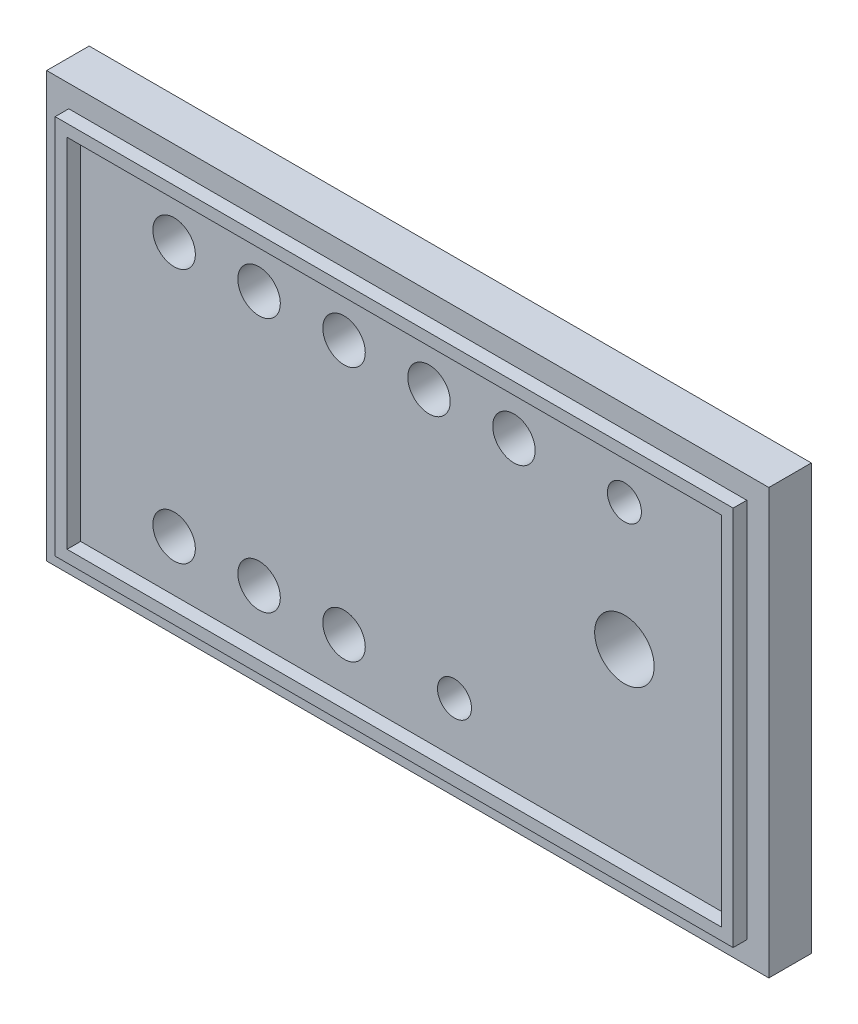
SolidWorks part; units mm, degrees
ref_plane "Přední rovina" through (0, 0, 0) normal (0, 0, 1) x (1, 0, 0)
ref_plane "Horní rovina" through (0, 0, 0) normal (0, 1, 0) x (1, 0, 0)
ref_plane "Pravá rovina" through (0, 0, 0) normal (1, 0, 0) x (0, 0, -1)
sketch "Skica1" plane through (0, 0, 0) normal (0, 0, 1) x (1, 0, 0)
  line L1 (0, 0) -> (85, 0)
  line L2 (0, 0) -> (0, 50)
  line L3 (0, 50) -> (85, 50)
  line L4 (85, 0) -> (85, 50)
  line L5 (2.6, 47.4) -> (82.4, 47.4)
  line L6 (2.6, 47.4) -> (2.6, 2.6)
  line L7 (2.6, 2.6) -> (82.4, 2.6)
  line L8 (82.4, 47.4) -> (82.4, 2.6)
  line L9 (2, 48) -> (83, 48)
  line L10 (2, 48) -> (2, 2)
  line L11 (2, 2) -> (83, 2)
  line L12 (83, 48) -> (83, 2)
  line L13 (4, 46) -> (81, 46)
  line L14 (4, 46) -> (4, 4)
  line L15 (4, 4) -> (81, 4)
  line L16 (81, 46) -> (81, 4)
  circle A0 centre (15, 10) radius 2.5
  circle A1 centre (25, 10) radius 2.5
  circle A2 centre (35, 10) radius 2.5
  circle A3 centre (15, 40) radius 2.5
  circle A4 centre (25, 40) radius 2.5
  circle A5 centre (35, 40) radius 2.5
  circle A6 centre (45, 40) radius 2.5
  circle A7 centre (55, 40) radius 2.5
  circle A8 centre (68, 40) radius 2
  circle A9 centre (68, 25) radius 3.5
  circle A10 centre (48, 10) radius 2
  point P39 (0, 0)
  point P40 (0, 0)
  point P41 (0, 0)
  dimension "D4" = 5
  dimension "D3" = 5
  dimension "D5" = 5
  dimension "D6" = 5
  dimension "D7" = 5
  dimension "D8" = 4
  dimension "D9" = 7
  dimension "D10" = 4
  dimension "D11" = 5
  dimension "D12" = 5
  dimension "D13" = 5
  dimension "D1" = 85
  dimension "D2" = 50
  dimension "D14" = 10
  dimension "D15" = 15
  dimension "D16" = 10
  dimension "D17" = 10
  dimension "D18" = 13
  dimension "D19" = 10
  dimension "D20" = 15
  dimension "D21" = 10
  dimension "D22" = 10
  dimension "D23" = 10
  dimension "D24" = 10
  dimension "D25" = 13
  dimension "D26" = 25
  dimension "D27" = 1.4
  dimension "D28" = 0.6
  dimension "D29" = 1.4
  dimension "D30" = 0.6
  dimension "D31" = 1.4
  dimension "D32" = 0.6
  dimension "D33" = 1.4
  dimension "D34" = 0.6
  dimension "D35" = 4
  dimension "D36" = 4
  dimension "D37" = 4
  dimension "D38" = 4
extrude "Přidat vysunutím2" add sketch "Skica1" along normal blind 5 contours A3 | A4 | A5 | A6 | A7 | A8 | A9 | A2 | A10 | A1 | A0 | L3 L4 L1 L2 region at (15, 10, 0) region at (25, 10, 0) region at (35, 10, 0) region at (15, 40, 0) region at (25, 40, 0) region at (35, 40, 0) region at (45, 40, 0) region at (55, 40, 0) region at (68, 40, 0) region at (68, 25, 0) region at (48, 10, 0)
extrude "Přidat vysunutím3" add sketch "Skica1<4>" along normal blind 6.6 contours L8 L5 L6 L7 L13 L16 L15 L14 region at (42.5, 46.4848, 0)
sketch "Skica1<4>" plane through (0, 0, 0) normal (0, 0, 1) x (1, 0, 0) same geometry as "Skica1"
